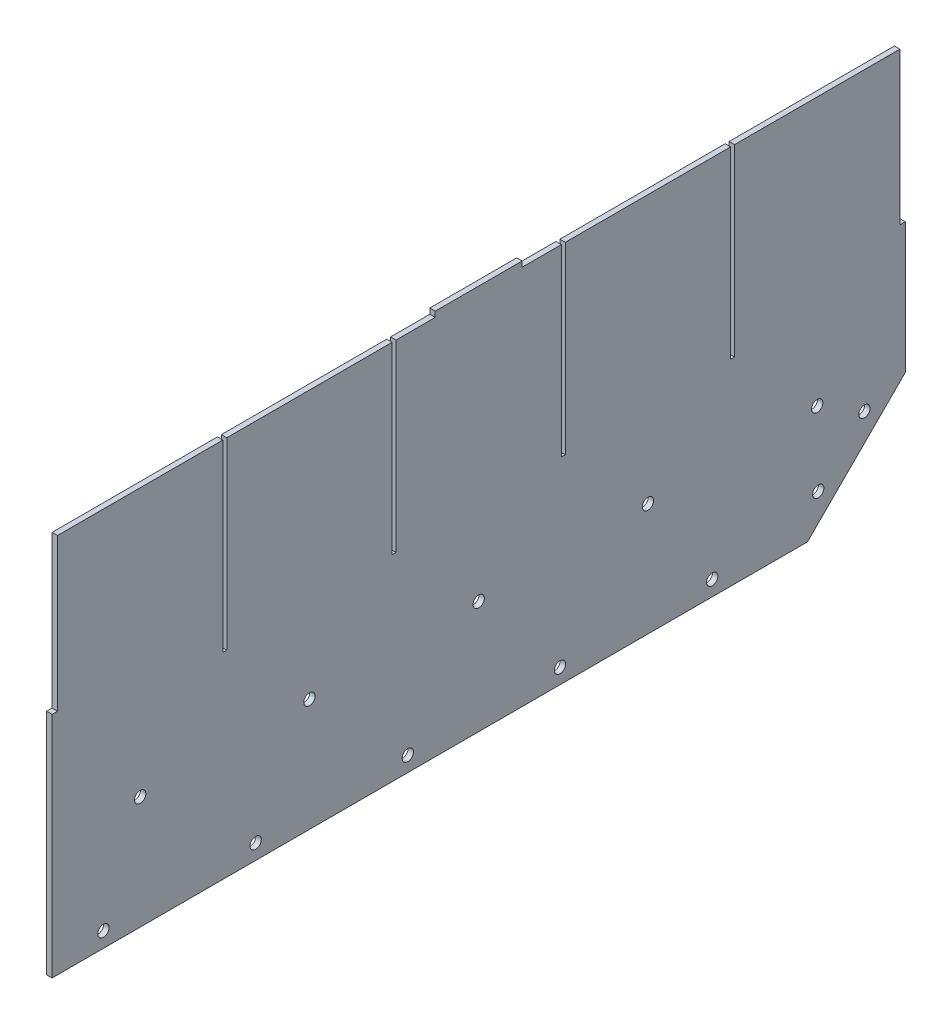
SolidWorks part; units mm, degrees
material "6061-T6 (SS)"
ref_plane "X-Y Datum" through (0, 0, 0) normal (0, 0, 1) x (1, 0, 0)
ref_plane "X-Z Datum" through (0, 0, 0) normal (0, 1, 0) x (1, 0, 0)
ref_plane "Y-Z Datum" through (0, 0, 0) normal (1, 0, 0) x (0, 0, -1)
sketch "Sketch1" plane through (0, 0, 0) normal (1, 0, 0) x (0, 0, -1)
  line L1 (-249.174, 82.55) -> (249.174, 82.55)
  line L2 (-249.174, 82.55) -> (-249.174, -82.55)
  line L3 (-249.174, -82.55) -> (249.174, -82.55)
  line L4 (249.174, 82.55) -> (249.174, -82.55)
  line L5 (-249.174, 82.55) -> (249.174, -82.55) construction
  line L6 (-249.174, -82.55) -> (249.174, 82.55) construction
  point P0 (0, 0)
  dimension "D1" = 165.1
  dimension "D2" = 498.348
extrude "Boss-Extrude1" add sketch "Sketch1" along normal mid plane 3.175
sketch "Sketch2" plane through (1.5875, 0, 0) normal (1, 0, 0) x (0, 0, -1)
  line L3 (192.024, -139.7) -> (-249.174, -139.7)
  line L5 (-249.174, -82.55) -> (249.174, -82.55) construction
  line L6 (-249.174, -82.55) -> (249.174, -82.55)
  line L7 (-249.174, -82.55) -> (-249.174, -139.7)
  line L12 (192.024, -139.7) -> (249.174, -82.55)
  line M10 (-249.174, -82.55) -> (249.174, -82.55)
  dimension "D1" = 45
  dimension "D5" = 57.15
extrude "Boss-Extrude2" add sketch "Sketch2" against normal blind 3.175 contours L3 L12 M10 region at (1.5875, -110.5456, 13.9978)
sketch "Sketch3" plane through (1.5875, 0, 0) normal (1, 0, 0) x (0, 0, -1)
  line L0 (-219.202, -139.7) -> (-219.202, -130.81)
  line L1 (192.024, -139.7) -> (-249.174, -139.7) construction
  line L2 (-219.202, -130.81) -> (-249.174, -130.81)
  line L3 (-249.174, 82.55) -> (-249.174, -139.7) construction
  circle A0 centre (-219.202, -130.81) radius 3.302
  dimension "D1" = 29.972
  dimension "D3" = 6.604
  dimension "D2" = 8.89
extrude "Cut-Extrude1" cut sketch "Sketch3" against normal blind 3.175 contours L2 A0 L0 | L0 A0 L2 region at (1.5875, -132.2114, 220.6034) region at (1.5875, -130.3429, 218.7349)
pattern_linear "LPattern1" count 5 spacing 88.9 along (0, 0, -1) of "Cut-Extrude1"
sketch "Sketch4" plane through (1.5875, 0, 0) normal (1, 0, 0) x (0, 0, -1)
  line L0 (192.024, -139.7) -> (183.9418, -131.6178)
  line L1 (183.9418, -131.6178) -> (198.3102, -117.2494)
  circle A0 centre (198.3102, -117.2494) radius 3.302
  dimension "D1" = 6.604
extrude "Cut-Extrude2" cut sketch "Sketch4" against normal through all contours A0 region at (1.5875, -120.2137, -199.5381)
pattern_linear "LPattern2" count 2 spacing 38.1 along (0, 0.7071, -0.7071) of "Cut-Extrude2"
sketch "Sketch5" plane through (-1.5875, 0, 0) normal (-1, 0, 0) x (0, 0, 1)
  line L1 (-249.174, 82.55) -> (-245.999, 82.55)
  line L2 (-249.174, 82.55) -> (-249.174, -6.35)
  line L3 (-249.174, -6.35) -> (-245.999, -6.35)
  line L4 (-245.999, 82.55) -> (-245.999, -6.35)
  line L5 (249.174, 82.55) -> (245.999, 82.55)
  line L6 (249.174, 82.55) -> (249.174, -6.35)
  line L7 (249.174, -6.35) -> (245.999, -6.35)
  line L8 (245.999, 82.55) -> (245.999, -6.35)
  dimension "D1" = 3.175
  dimension "D2" = 88.9
  dimension "D3" = 3.175
  dimension "D4" = 88.9
extrude "Cut-Extrude3" cut sketch "Sketch5" against normal through all
sketch "Sketch6" plane through (-1.5875, 0, 0) normal (-1, 0, 0) x (0, 0, 1)
  line L1 (-149.4282, 82.55) -> (-149.4282, -24.892) construction
  line L2 (-122.174, 82.55) -> (-249.174, 82.55)
  line L3 (-149.4282, 82.55) -> (-149.4282, -24.892)
  line L5 (-149.4282, 82.55) -> (-147.1422, 82.55)
  line L6 (-149.4282, 82.55) -> (-149.4282, -24.892)
  line L7 (-149.4282, -24.892) -> (-147.1422, -24.892)
  line L8 (-147.1422, 82.55) -> (-147.1422, -24.892)
  dimension "D1" = 2.286
  dimension "D2" = 107.442
extrude "Cut-Extrude4" cut sketch "Sketch6" against normal through all contours L8 L2 L3 L7 region at (-1.5875, 28.829, -148.2852)
pattern_linear "LPattern3" count 4 spacing 98.8568 along (0, 0, 1) of "Cut-Extrude4"
sketch "Sketch7" plane through (-1.5875, 0, 0) normal (-1, 0, 0) x (0, 0, 1)
  line L0 (122.174, 85.725) -> (25.4, 85.725) construction
  line L1 (25.4, 82.55) -> (-25.4, 82.55)
  line L2 (25.4, 82.55) -> (25.4, 85.725)
  line L3 (25.4, 85.725) -> (-25.4, 85.725)
  line L4 (-25.4, 82.55) -> (-25.4, 85.725)
  line L5 (25.4, 82.55) -> (-25.4, 85.725) construction
  line L6 (25.4, 85.725) -> (-25.4, 82.55) construction
  point P0 (0, 84.1375)
  dimension "D1" = 3.175
  dimension "D2" = 50.8
extrude "Boss-Extrude3" add sketch "Sketch7" against normal blind 3.175
sketch "Sketch8" plane through (1.5875, 0, 0) normal (1, 0, 0) x (0, 0, -1)
  line L0 (192.024, -139.7) -> (-249.174, -139.7) construction
  circle A0 centre (0, -73.8124) radius 3
  dimension "D1" = 6
  dimension "D2" = 65.8876
hole_wizard "M6 Clearance Hole1" positions "Sketch9" profile "Sketch10" hole size "M6" standard "ANSI Metric" end condition through all
sketch "Sketch9" plane through (1.5875, 0, 0) normal (1, 0, 0) x (0, 0, -1)
  point P0 (0, -73.8124)
sketch "Sketch10" plane through (1.5875, -73.8124, 0) normal (0, 1, 0) x (0, 0, -1)
  line L0 (0, 0) -> (0, 3.175)
  line L1 (0, 3.175) -> (3.3, 3.175)
  line L2 (3.3, 3.175) -> (3.3, 0)
  line L5 (3.3, 0) -> (0, 0)
  line L11 (0, -6.35) -> (0, 107.95) construction
  dimension "Thru Hole Dia." = 6.6
  dimension "Thru Hole Depth" = 3.175
pattern_linear "LPattern4" count 3 spacing 98.8568 along (0, 0, 1) count 3 spacing 98.8568 along (0, 0, -1) of "M6 Clearance Hole1"
